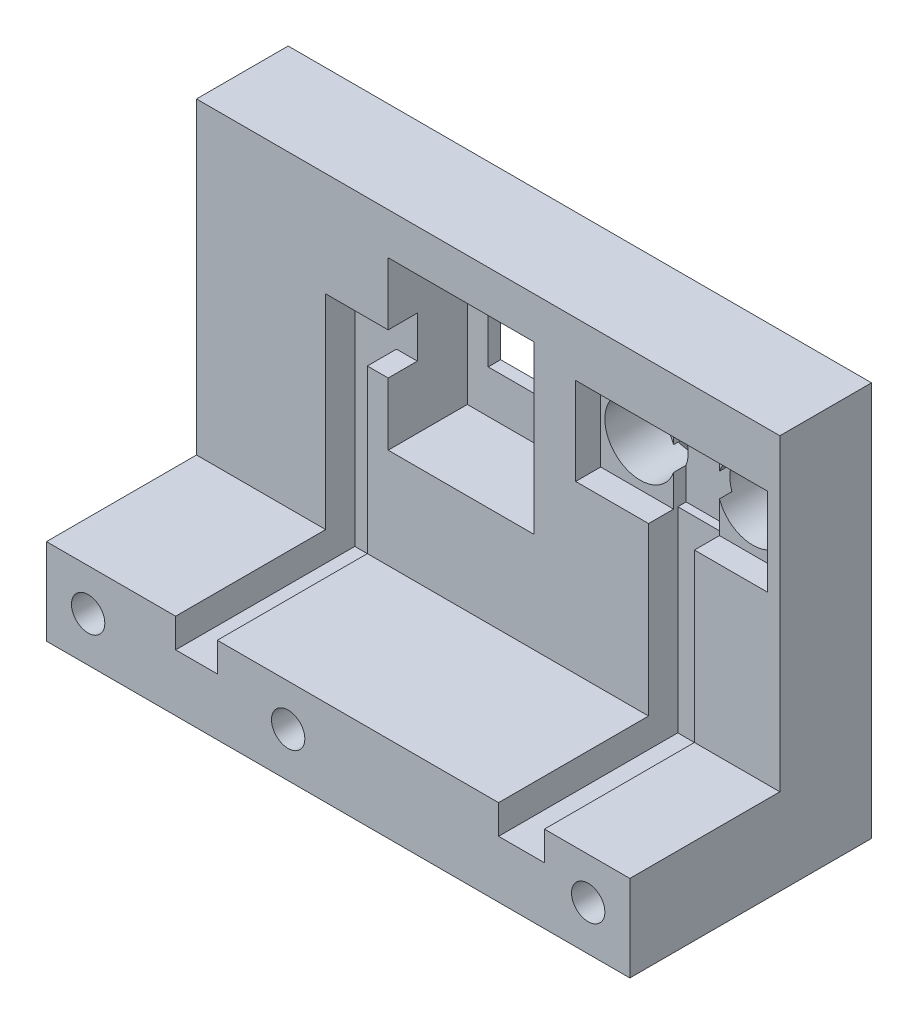
SolidWorks part; units mm, degrees
ref_plane "Front Plane" through (0, 0, 0) normal (0, 0, 1) x (1, 0, 0)
ref_plane "Top Plane" through (0, 0, 0) normal (0, 1, 0) x (1, 0, 0)
ref_plane "Right Plane" through (0, 0, 0) normal (1, 0, 0) x (0, 0, -1)
sketch "Sketch1" plane through (0, 0, 0) normal (0, 0, 1) x (1, 0, 0)
  line L1 (0, 0) -> (92, 0)
  line L2 (0, 0) -> (0, 31.276)
  line L3 (0, 31.276) -> (92, 31.276)
  line L4 (92, 0) -> (92, 31.276)
  line L5 (0, 0) -> (92, 0)
  line L6 (0, 0) -> (0, 3.6974)
  line L7 (0, 3.6974) -> (92, 3.6974)
  line L8 (92, 0) -> (92, 3.6974)
  line L9 (0, 31.276) -> (31.9549, 31.276)
  line L10 (0, 31.276) -> (0, 3.6974)
  line L11 (0, 3.6974) -> (31.9549, 3.6974)
  line L12 (31.9549, 31.276) -> (31.9549, 3.6974)
  line L13 (31.9549, 31.276) -> (92, 31.276)
  line L14 (31.9549, 31.276) -> (31.9549, 3.6974)
  line L15 (31.9549, 3.6974) -> (92, 3.6974)
  line L16 (92, 31.276) -> (92, 3.6974)
  dimension "D1" = 92
extrude "Bottom section" add sketch "Sketch1" along normal blind 36 contours L7 L2 L1 L4 region at (46, 1.8487, 0)
ref_plane "Plane for PIR side" through (40, 0, 0) normal (-1, 0, 0) x (0, 0, 1)
sketch "Sketch2" plane through (40, 0, 0) normal (-1, 0, 0) x (0, 0, 1)
  line L0 (0, 3.6974) -> (0, 77.6974)
  line L1 (0, 77.6974) -> (-30, 77.6974)
  line L2 (0, 3.6974) -> (-19, 3.6974)
  line L3 (-19, 3.6974) -> (-19, 47.4752)
  line L4 (-19, 47.4752) -> (-30, 77.6974)
  dimension "D1" = 70
  dimension "D2" = 74
  dimension "D3" = 30
  dimension "D4" = 19
extrude "PIR Housing" add sketch "Sketch2" along normal up to vertex (40 mm away) separate body up to point (0, 3.6974, 0)
sketch "Sketch3" plane through (0, 0, 0) normal (0, 0, -1) x (-1, 0, 0)
  line L1 (-92, 3.6974) -> (-40, 3.6974)
  line L2 (-92, 3.6974) -> (-92, 77.6974)
  line L3 (-92, 77.6974) -> (-40, 77.6974)
  line L4 (-40, 3.6974) -> (-40, 77.6974)
extrude "Sonar Housing" add sketch "Sketch3" along normal blind 19
sketch "Sketch4" plane through (0, 0, 36) normal (0, 0, 1) x (1, 0, 0)
  line L1 (92, 0) -> (0, 0)
  line L2 (92, 0) -> (92, 77.6974)
  line L3 (92, 77.6974) -> (0, 77.6974)
  line L4 (0, 0) -> (0, 77.6974)
extrude "Backing" add sketch "Sketch4" along normal blind 10
sketch "Sketch6" plane through (0, 0, 0) normal (0, 0, 1) x (1, 0, 0)
  line L0 (92, 77.6974) -> (92, 3.6974) construction
  line L1 (89, 53.6974) -> (43, 53.6974)
  line L2 (89, 53.6974) -> (89, 74.6974)
  line L3 (89, 74.6974) -> (43, 74.6974)
  line L4 (43, 53.6974) -> (43, 74.6974)
  line L5 (89, 53.6974) -> (43, 74.6974) construction
  line L6 (89, 74.6974) -> (43, 53.6974) construction
  line L9 (0, 77.6974) -> (40, 77.6974) construction
  point P0 (66, 64.1974)
  dimension "D1" = 46
  dimension "D2" = 21
  dimension "D3" = 3
  dimension "D4" = 3
extrude "Main enclosure for sonar" cut sketch "Sketch6" against normal blind 6
sketch "Sketch7" plane through (0, 0, 0) normal (0, 0, 1) x (1, 0, 0)
  line L1 (60.5, 53.6974) -> (71.5, 53.6974)
  line L2 (60.5, 53.6974) -> (60.5, 50.6974)
  line L3 (60.5, 50.6974) -> (71.5, 50.6974)
  line L4 (71.5, 53.6974) -> (71.5, 50.6974)
  line L6 (43, 53.6974) -> (89, 53.6974) construction
  point P6 (66, 53.6974)
  point P7 (66, 53.6974)
  dimension "D1" = 11
  dimension "D2" = 3
extrude "Gap for Sonar Wiring" cut sketch "Sketch7" against normal blind 3
sketch "Sketch8" plane through (0, 0, -6) normal (0, 0, 1) x (1, 0, 0)
  line L0 (43, 64.1974) -> (89, 64.1974) construction
  line L1 (43, 74.6974) -> (43, 53.6974) construction
  line L2 (89, 53.6974) -> (89, 74.6974) construction
  line L3 (66, 74.6974) -> (66, 53.6974) construction
  line L4 (89, 74.6974) -> (43, 74.6974) construction
  line L5 (43, 53.6974) -> (89, 53.6974) construction
  line L6 (44, 64.1974) -> (44, 74.6974)
  line L7 (88, 64.1974) -> (88, 53.6974)
  circle A0 centre (79.5, 64.1974) radius 8.5
  circle A1 centre (52.5, 64.1974) radius 8.5
  dimension "D1" = 17
  dimension "D2" = 17
  dimension "D3" = 1
  dimension "D4" = 1
extrude "2 Holes for Sonar" cut sketch "Sketch8" against normal blind 13 contours A0 | A1 region at (79.5, 64.1974, -6) region at (52.5, 64.1974, -6)
sketch "Sketch11" plane through (0, 0, -6) normal (0, 0, 1) x (1, 0, 0)
  line L0 (43, 53.6974) -> (89, 53.6974) construction
  line L1 (71.5, 53.6974) -> (60.5, 53.6974)
  line L2 (71.5, 53.6974) -> (71.5, 74.6974)
  line L3 (71.5, 74.6974) -> (60.5, 74.6974)
  line L4 (60.5, 53.6974) -> (60.5, 74.6974)
  line L5 (89, 74.6974) -> (43, 74.6974) construction
  line L6 (89, 53.6974) -> (89, 74.6974) construction
  dimension "D1" = 11
  dimension "D2" = 17.5
extrude "Center gap for sonar component" cut sketch "Sketch11" against normal blind 3
sketch "Min Clearance Line for Sonar Wiring" plane through (0, 0, 0) normal (0, 0, 1) x (1, 0, 0)
  line L0 (-918.1, 35.6974) -> (49081.9, 35.6974) construction
  line L3 (60.5, 50.6974) -> (71.5, 50.6974) construction
  dimension "D1" = 15
shell "Main Enclosure for PIR sensor" thickness 3 removed face at (20, 40.6974, 0)
sketch "Sketch20" plane through (0, -0.5529, -1.5192) normal (0, -0.342, -0.9397) x (-1, 0, 0)
  line L0 (-40, 67.1914) -> (0, 67.1914) construction
  line L3 (-20, 83.2723) -> (-20, 51.1105) construction
  line L4 (0, 83.2723) -> (-40, 83.2723) construction
  line L5 (0, 51.1105) -> (-40, 51.1105) construction
  line L6 (-40, 83.2723) -> (-40, 51.1105) construction
  line L7 (0, 83.2723) -> (0, 51.1105) construction
  circle A0 centre (-20, 67.1914) radius 11.5
  dimension "D1" = 23
extrude "Hole for PIR sensor" cut sketch "Sketch20" against normal blind 3
sketch "Sketch21" plane through (0, 0, -16) normal (0, 0, 1) x (1, 0, 0)
  line L1 (37, 48.0042) -> (3, 48.0042)
  line L2 (37, 48.0042) -> (37, 6.6974)
  line L3 (37, 6.6974) -> (3, 6.6974)
  line L4 (3, 48.0042) -> (3, 6.6974)
extrude "Extrude to Fill up bottom space of PIR cavity" add sketch "Sketch21" along normal up to vertex (16 mm away) up to point (3, 6.6974, 0)
sketch "Sketch22" plane through (0, 3.6974, 0) normal (0, 1, 0) x (1, 0, 0)
  line L0 (92, 0) -> (40, 0) construction
  line L1 (0, -36) -> (16, -36) construction
  line L2 (0, -36) -> (0, 0) construction
  line L3 (0, 0) -> (16, 0) construction
  line L4 (16, -36) -> (16, 0) construction
  line L5 (0, 0) -> (92, 0) construction
  line L6 (76, 0) -> (92, 0) construction
  line L7 (76, 0) -> (76, -36) construction
  line L8 (76, -36) -> (92, -36) construction
  line L9 (92, 0) -> (92, -36) construction
  line L11 (0, 0) -> (92, 0)
  line L12 (0, 0) -> (0, -36)
  line L13 (0, -36) -> (92, -36)
  line L14 (92, 0) -> (92, -36)
  dimension "D1" = 60
extrude "Elevated material for base" add sketch "Sketch22" along normal blind 10 separate body
sketch "Sketch24" plane through (92, 0, 0) normal (1, 0, 0) x (0, 0, -1)
  line L0 (19, 3.6974) -> (0, 3.6974)
  line L1 (19, 3.6974) -> (19, 0)
  line L2 (0, 3.6974) -> (0, 0)
  line L3 (19, 0) -> (0, 0)
  line L5 (0, 0) -> (0, 3.6974)
  line L6 (0, 3.6974) -> (-36, 3.6974)
  line L7 (-36, 3.6974) -> (-36, 77.6974)
  line L8 (-46, 0) -> (0, 0)
  line L9 (0, 0) -> (0, 3.6974)
  line L15 (-36, 3.6974) -> (-36, 77.6974)
  line L16 (-36, 77.6974) -> (-46, 77.6974)
  line L17 (-36, 77.6974) -> (-46, 77.6974)
  line L18 (-46, 77.6974) -> (-46, 0)
  line L19 (-46, 77.6974) -> (-46, 0)
  line M1 (0, 0) -> (0, 3.6974)
  dimension "D1" = 0
extrude "Base Material for PIR and Sonar casing overhang" add sketch "Sketch24" against normal up to vertex (92 mm away) contours L3 L1 L0 M1 region at (92, 1.8487, -9.5) up to point (0, 0, 0)
sketch "Sketch29" plane through (0, 77.6974, 0) normal (0, 1, 0) x (1, 0, 0)
  line L0 (0, 30) -> (40, 30)
  line L1 (40, 30) -> (40, 19)
  line L2 (40, 19) -> (92, 19)
  line L3 (92, 19) -> (92, 0)
  line L4 (92, 19) -> (92, 0) construction
  line L5 (92, 0) -> (0, 0)
  line L6 (0, 0) -> (0, 30)
  line L7 (0, -36) -> (0, -46)
  line L8 (0, -46) -> (92, -46)
  line L9 (92, -46) -> (92, -36)
  line L10 (92, -36) -> (0, -36)
  line M1 (0, 0) -> (92, 0)
  line M2 (92, 0) -> (92, 19)
  line M3 (92, 19) -> (40, 19)
  line M4 (40, 19) -> (40, 30)
  line M5 (40, 30) -> (0, 30)
  line M6 (0, 30) -> (0, 0)
extrude "Additional material to increase height of casing" add sketch "Sketch29" along normal blind 10 contours M6 M1 M2 M3 M4 M5 region at (40.7715, 77.6974, -12.5165)
sketch "Sketch56" plane through (0, 74.6974, 0) normal (0, -1, 0) x (1, 0, 0)
  line L0 (3, 0) -> (3, -25.7156) construction
  line L1 (37, -25.7156) -> (3, -25.7156)
  line L2 (37, -25.7156) -> (37, -12.7156)
  line L3 (37, -12.7156) -> (3, -12.7156)
  line L4 (3, -25.7156) -> (3, -12.7156)
  dimension "D1" = 13
extrude "Extra Upper space to fit PIR sensor" cut sketch "Sketch56" against normal blind 10
sketch "Sketch54" plane through (0, 77.6974, 0) normal (0, 1, 0) x (1, 0, 0)
  line L1 (0, -46) -> (92, -46)
  line L2 (0, -46) -> (0, -36)
  line L3 (0, -36) -> (92, -36)
  line L4 (92, -46) -> (92, -36)
extrude "Cut to remove Backing that Can't be removed" cut sketch "Sketch54" against normal up to next (77.6974 mm away)
sketch "Sketch60" plane through (0, 0, 36) normal (0, 0, 1) x (1, 0, 0)
  line L0 (28, 3.6974) -> (46, 3.6974) construction
  line L1 (46, 3.6974) -> (64, 3.6974) construction
  line L2 (0, 13.6974) -> (92, 13.6974) construction
  line L3 (0, 13.6974) -> (0, 3.6974) construction
  line L4 (0, 0) -> (0, 7.3949) construction
  line L5 (10, 3.6974) -> (28, 3.6974) construction
  line L6 (64, 3.6974) -> (82, 3.6974) construction
  line L7 (92, 13.6974) -> (92, 3.6974) construction
  line L8 (-114.8237, 3.6974) -> (114.8237, 3.6974) construction
  circle A0 centre (28, 3.6974) radius 4
  circle A1 centre (46, 3.6974) radius 4
  circle A2 centre (64, 3.6974) radius 4
  circle A3 centre (10, 3.6974) radius 4
  circle A4 centre (82, 3.6974) radius 4
  point P21 (0, 3.6974)
  dimension "D3" = 8
  dimension "D1" = 10
  dimension "D2" = 10
  dimension "D4" = 10
extrude "Boss-Extrude1" add sketch "Sketch60" along normal blind 27 contours A0 | A1 | A2
extrude "Cut to remove the rods sticking out that could not be easily removed" cut sketch "Sketch60<6>" along normal through all
sketch "Sketch60<6>" plane through (0, 0, 36) normal (0, 0, 1) x (1, 0, 0) same geometry as "Sketch60"
sketch "Sketch79" plane through (40, 0, 0) normal (1, 0, 0) x (0, 0, -1)
  line L4 (19, 87.6974) -> (19, 47.4752)
  line L5 (19, 47.4752) -> (30, 77.6974)
  line L6 (30, 77.6974) -> (30, 87.6974)
  line L7 (30, 87.6974) -> (19, 87.6974)
  line L8 (19, 87.6974) -> (19, 47.4752)
  line L9 (19, 47.4752) -> (30, 77.6974)
  line L10 (30, 77.6974) -> (30, 87.6974)
  line L11 (30, 87.6974) -> (19, 87.6974)
  dimension "D1" = 0
extrude "Cut-Extrude15" cut sketch "Sketch79" against normal up to next
sketch "Sketch81" plane through (0, 0, -12.7156) normal (0, 0, -1) x (-1, 0, 0)
  line L0 (-37, 84.6974) -> (-3, 84.6974) construction
  line L1 (-37, 84.6974) -> (-3, 84.6974)
  line L2 (-3, 84.6974) -> (-3, 74.6974) construction
  line L3 (-3, 84.6974) -> (-3, 74.6974)
  line L8 (-37, 74.6974) -> (-3, 74.6974)
  line L9 (-3, 74.6974) -> (-3, 84.6974)
  line L10 (-3, 84.6974) -> (-37, 84.6974)
  line L11 (-37, 84.6974) -> (-37, 74.6974)
  line L12 (-37, 74.6974) -> (-3, 74.6974)
  line L13 (-3, 74.6974) -> (-3, 84.6974)
  line L14 (-3, 84.6974) -> (-37, 84.6974)
  line L15 (-37, 84.6974) -> (-37, 74.6974)
  line M6 (-3, 74.6974) -> (-3, 84.6974)
  line M7 (-3, 84.6974) -> (-37, 84.6974)
  line M8 (-37, 84.6974) -> (-37, 74.6974)
  dimension "D1" = 0
extrude "Boss-Extrude7" add sketch "Sketch81" along normal through all contours M8 M6 M7 region at (20, 79.6974, -12.7156)
sketch "Sketch82" plane through (0, 0, 0) normal (0, 0, 1) x (1, 0, 0)
  line L1 (-2, 37.6974) -> (33, 37.6974)
  line L2 (-2, 37.6974) -> (-2, 77.6974)
  line L3 (-2, 77.6974) -> (33, 77.6974)
  line L4 (33, 37.6974) -> (33, 77.6974)
  line L5 (-2, 37.6974) -> (33, 77.6974) construction
  line L6 (-2, 77.6974) -> (33, 37.6974) construction
  line L10 (43, 74.6974) -> (43, 53.6974) construction
  line L11 (0, 87.6974) -> (92, 87.6974) construction
  line L13 (3, 45.1974) -> (28, 45.1974)
  line L14 (3, 45.1974) -> (3, 70.1974)
  line L15 (3, 70.1974) -> (28, 70.1974)
  line L16 (28, 45.1974) -> (28, 70.1974)
  line L17 (3, 45.1974) -> (28, 70.1974) construction
  line L18 (3, 70.1974) -> (28, 45.1974) construction
  point P0 (15.5, 57.6974)
  point P9 (15.5, 57.6974)
  line M34 (37, 48.0042) -> (3, 48.0042)
  line M35 (3, 48.0042) -> (3, 74.6974)
  dimension "D1" = 35
  dimension "D2" = 40
  dimension "D3" = 10
  dimension "D4" = 10
  dimension "D5" = 25
  dimension "D6" = 25
sketch "Sketch86" plane through (0, 0, 0) normal (0, 0, 1) x (1, 0, 0)
  line L0 (3, 74.6974) -> (37, 74.6974) construction
  line L1 (3, 74.6974) -> (37, 74.6974)
  line L2 (37, 48.0042) -> (37, 74.6974) construction
  line L3 (37, 48.0042) -> (37, 74.6974)
  line L4 (37, 48.0042) -> (3, 48.0042) construction
  line L5 (37, 48.0042) -> (3, 48.0042)
  line L6 (3, 48.0042) -> (3, 74.6974) construction
  line L7 (3, 48.0042) -> (3, 74.6974)
extrude "Boss-Extrude9" add sketch "Sketch86" against normal through all
sketch "Sketch87" plane through (0, 0, 0) normal (-1, 0, 0) x (0, 0, 1)
  line L6 (0, 87.6974) -> (-19, 87.6974)
  line L7 (-19, 87.6974) -> (-19, 0)
  line L8 (-19, 0) -> (36, 0)
  line L9 (36, 0) -> (36, 13.6974)
  line L10 (36, 13.6974) -> (0, 13.6974)
  line L11 (0, 13.6974) -> (0, 87.6974)
  line L12 (0, 87.6974) -> (-19, 87.6974)
  line L13 (-19, 87.6974) -> (-19, 0)
  line L14 (-19, 0) -> (36, 0)
  line L15 (36, 0) -> (36, 13.6974)
  line L16 (36, 13.6974) -> (0, 13.6974)
  line L17 (0, 13.6974) -> (0, 87.6974)
  dimension "D1" = 0
extrude "Addition of material to side 48mm" add sketch "Sketch87" along normal blind 48
extrude "Cut-Extrude20" cut sketch "Sketch82" against normal blind 19 contours L3 L4 L1 L2
sketch "Sketch88" plane through (0, 0, -19) normal (0, 0, -1) x (-1, 0, 0)
  line L0 (2, 37.6974) -> (-33, 37.6974) construction
  line L1 (2, 37.6974) -> (-33, 37.6974)
  line L2 (-33, 37.6974) -> (-33, 77.6974) construction
  line L3 (-33, 37.6974) -> (-33, 77.6974)
  line L4 (-92, 0) -> (48, 0)
  line L5 (48, 0) -> (48, 87.6974)
  line L6 (48, 87.6974) -> (-92, 87.6974)
  line L7 (-92, 87.6974) -> (-92, 0)
  line L8 (-92, 0) -> (48, 0)
  line L9 (48, 0) -> (48, 87.6974)
  line L10 (48, 87.6974) -> (-92, 87.6974)
  line L11 (-92, 87.6974) -> (-92, 0)
  line L12 (2, 77.6974) -> (-33, 77.6974) construction
  line L13 (2, 77.6974) -> (-33, 77.6974)
  line L14 (2, 37.6974) -> (2, 77.6974) construction
  line L15 (2, 37.6974) -> (2, 77.6974)
  circle M5 centre (-79.5, 64.1974) radius 8.5
  circle M6 centre (-52.5, 64.1974) radius 8.5
  line M7 (-92, 0) -> (48, 0)
  line M8 (48, 0) -> (48, 87.6974)
  line M9 (48, 87.6974) -> (-92, 87.6974)
  line M10 (-92, 87.6974) -> (-92, 0)
  line M11 (2, 77.6974) -> (2, 37.6974)
  line M12 (2, 37.6974) -> (-33, 37.6974)
  line M13 (-33, 37.6974) -> (-33, 77.6974)
  line M14 (-33, 77.6974) -> (2, 77.6974)
  dimension "D1" = 0
extrude "Boss-Extrude11" add sketch "Sketch88" along normal blind 3 contours M11 M14 M13 M12 | M10 M7 M8 M9 M6 M14 M11 M12 M13 M5 region at (15.5, 57.6974, -19) region at (90.348, 43.8487, -19)
sketch "Sketch91" plane through (0, 0, 0) normal (0, -1, 0) x (1, 0, 0)
  line L1 (92, 36) -> (-48, 36)
  line L2 (92, 36) -> (92, -22)
  line L3 (92, -22) -> (-48, -22)
  line L4 (-48, 36) -> (-48, -22)
extrude "Addition of material to base 7mm " add sketch "Sketch91" along normal blind 7 contours L1 L4 L3 L2
chamfer "Chamfer1" distance 4 angle 45 1 edges at (44, 64.1974, -22)
chamfer "Chamfer2" distance 4 angle 45 1 edges at (71, 64.1974, -22)
extrude "Cut-Extrude21" cut sketch "Sketch82<3>" against normal through all contours L16 L15 M34 M35 region at (15.5, 59.1008, 0)
sketch "Sketch82<3>" plane through (0, 0, 0) normal (0, 0, 1) x (1, 0, 0) same geometry as "Sketch82"
sketch "Sketch89" plane through (0, 0, 0) normal (0, 0, 1) x (1, 0, 0)
  line L0 (-2, 37.6974) -> (-2, 77.6974) construction
  line L1 (-2, 62.6974) -> (-17, 62.6974)
  line L2 (-2, 62.6974) -> (-2, 52.6974)
  line L3 (-2, 52.6974) -> (-17, 52.6974)
  line L4 (-17, 62.6974) -> (-17, 52.6974)
  line L5 (92, 13.6974) -> (-48, 13.6974) construction
  line L6 (-17, 52.6974) -> (-7, 52.6974)
  line L7 (-17, 52.6974) -> (-17, 6.6974)
  line L8 (-17, 6.6974) -> (-7, 6.6974)
  line L9 (-7, 52.6974) -> (-7, 6.6974)
  line L10 (60.5, 50.6974) -> (71.5, 50.6974)
  line L11 (60.5, 50.6974) -> (60.5, 6.6974)
  line L12 (71.5, 50.6974) -> (71.5, 6.6974)
  line L13 (60.5, 6.6974) -> (71.5, 6.6974)
  line L15 (71.5, 50.6974) -> (60.5, 50.6974)
  line L16 (71.5, 50.6974) -> (71.5, 53.6974)
  line L17 (71.5, 53.6974) -> (60.5, 53.6974)
  line L18 (60.5, 50.6974) -> (60.5, 53.6974)
  point P6 (-2, 57.6974)
  point P7 (-2, 57.6974)
  line M4 (60.5, 50.6974) -> (60.5, 53.6974)
  line M10 (71.5, 53.6974) -> (71.5, 50.6974)
  line M11 (71.5, 50.6974) -> (60.5, 50.6974)
  line M14 (-48, 13.6974) -> (92, 13.6974)
  line M17 (-2, 37.6974) -> (-2, 77.6974)
  dimension "D1" = 10
  dimension "D2" = 15
  dimension "D3" = 10
  dimension "D4" = 7
  dimension "D5" = 7
extrude "Cut-Extrude22" cut sketch "Sketch89" against normal blind 7 contours L9 L3 L7 M14 | L1 L4 L3 M17 | L17 M10 M4 M11 | L12 L13 L11 L10 | L7 L8 L9 L6 region at (-9.5, 57.6974, 0) region at (-12, 33.1974, 0) region at (66, 52.1974, 0)
sketch "Sketch90" plane through (0, 13.6974, 0) normal (0, 1, 0) x (1, 0, 0)
  line L0 (60.5, 0) -> (71.5, 0)
  line L1 (60.5, 0) -> (60.5, -36)
  line L2 (71.5, 0) -> (71.5, -36)
  line L3 (60.5, -36) -> (71.5, -36)
  line L4 (-17, 0) -> (-7, 0)
  line L5 (-17, 0) -> (-17, -36)
  line L6 (-7, 0) -> (-7, -36)
  line L7 (-17, -36) -> (-7, -36)
  line L8 (-48, -36) -> (92, -36) construction
  dimension "D1" = 0
  dimension "D2" = 0
extrude "Cut-Extrude23" cut sketch "Sketch90" against normal blind 7
extrude "Cut-Extrude6" cut sketch "Sketch60<5>" against normal blind 15 contours A3 | A4
sketch "Sketch60<5>" plane through (0, 0, 36) normal (0, 0, 1) x (1, 0, 0) same geometry as "Sketch60"
sketch "Sketch93" plane through (0, 0, 36) normal (0, 0, 1) x (1, 0, 0)
  line L0 (-48, -7) -> (-48, 13.6974) construction
  line L1 (-48, 13.6974) -> (-17, 13.6974) construction
  circle A0 centre (-38, 3.6974) radius 4
  point P6 (-36.2113, -7)
  point P7 (-35.9943, 76.9872)
  point P8 (-40.9285, -7)
  dimension "D1" = 8
  dimension "D2" = 10
  dimension "D3" = 10
extrude "Cut-Extrude24" cut sketch "Sketch93" against normal blind 15
sketch "Sketch94" plane through (0, 0, -22) normal (0, 0, -1) x (-1, 0, 0)
  line L0 (30.1719, 87.6974) -> (30.1719, -7) construction
  line L1 (48, 87.6974) -> (-92, 87.6974) construction
  line L2 (-92, -7) -> (48, -7) construction
  text T0 "<b>STATION 1</b>" font "Century Gothic" height 5
extrude "Cut-Extrude25" cut sketch "Sketch94" against normal blind 2
